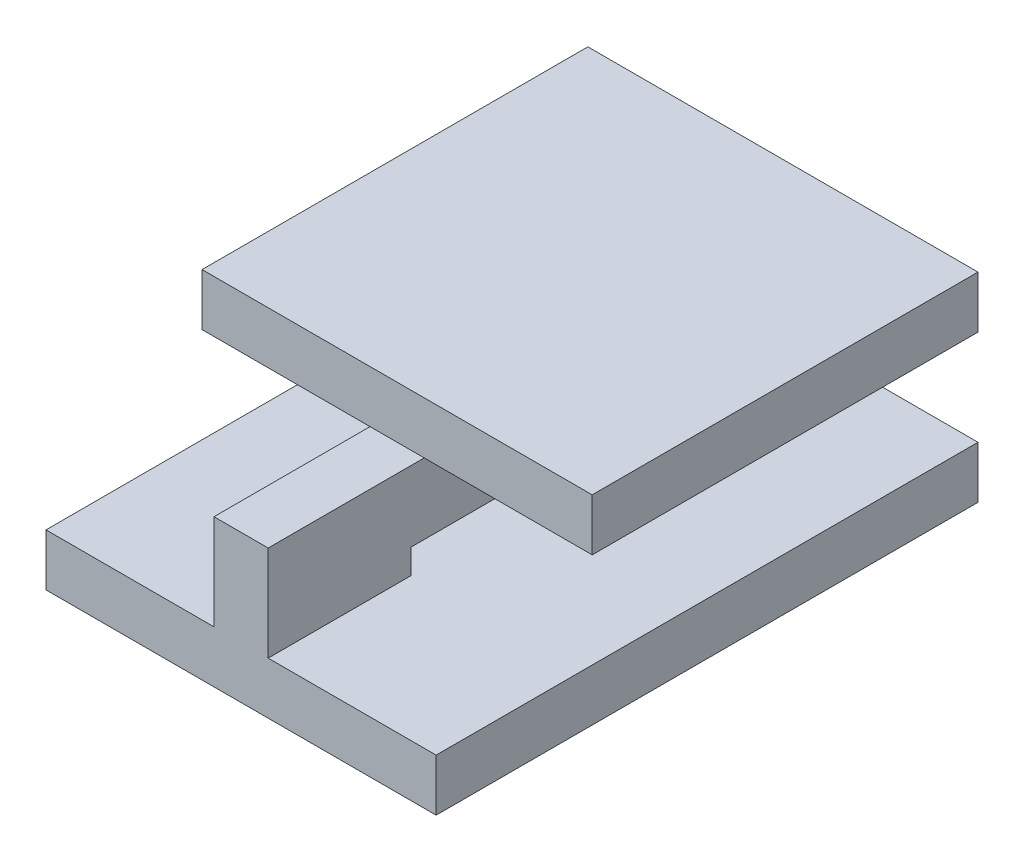
SolidWorks part; units mm, degrees
ref_plane "Front Plane" through (0, 0, 0) normal (0, 0, 1) x (1, 0, 0)
ref_plane "Top Plane" through (0, 0, 0) normal (0, 1, 0) x (1, 0, 0)
ref_plane "Right Plane" through (0, 0, 0) normal (1, 0, 0) x (0, 0, -1)
sketch "Sketch1" plane through (0, 0, 0) normal (0, 1, 0) x (1, 0, 0)
  line L1 (0, 0) -> (90, 0)
  line L2 (0, 0) -> (0, 125)
  line L3 (0, 125) -> (90, 125)
  line L4 (90, 0) -> (90, 125)
  dimension "D1" = 90
  dimension "D2" = 125
extrude "Boss-Extrude1" add sketch "Sketch1" along normal blind 12
sketch "Sketch2" plane through (0, 12, 0) normal (0, 1, 0) x (1, 0, 0)
  line L0 (0, 0) -> (90, 0) construction
  line L1 (38.75, 0) -> (51.25, 0)
  line L2 (38.75, 0) -> (38.75, 125)
  line L3 (38.75, 125) -> (51.25, 125)
  line L4 (51.25, 0) -> (51.25, 125)
  line L5 (90, 125) -> (0, 125) construction
  point P8 (45, 0)
  point P9 (45, 0)
  dimension "D1" = 12.5
extrude "Boss-Extrude2" add sketch "Sketch2" along normal blind 22
sketch "Sketch3" plane through (0, 34, 0) normal (0, 1, 0) x (1, 0, 0)
  line L1 (0, 125) -> (90, 125)
  line L2 (0, 125) -> (0, 36)
  line L3 (0, 36) -> (90, 36)
  line L4 (90, 125) -> (90, 36)
  line L5 (38.75, 125) -> (0, 125) construction
  line L6 (45, 125) -> (45, 0)
  line L8 (51.25, 125) -> (38.75, 125) construction
  line L9 (38.75, 0) -> (51.25, 0) construction
  point P15 (45, 125)
  line M7 (38.75, 125) -> (38.75, 0)
  line M9 (51.25, 0) -> (51.25, 125)
  line M10 (51.25, 125) -> (38.75, 125)
  dimension "D1" = 89
  dimension "D2" = 90
extrude "Boss-Extrude3" add sketch "Sketch3" along normal blind 12 contours L4 L1 L3 M9 | L2 L3 L1 M7 | L6 L1 L3 M7 | L6 L3 M10 M9 region at (19.375, 34, -80.5) region at (41.875, 34, -80.5) region at (48.125, 34, -80.5) region at (70.625, 34, -80.5)
sketch "Sketch4" plane through (51.25, 0, 0) normal (1, 0, 0) x (0, 0, -1)
  line L1 (125, 12) -> (32.9566, 12)
  line L2 (125, 12) -> (125, 17.6974)
  line L3 (125, 17.6974) -> (32.9566, 17.6974)
  line L4 (32.9566, 12) -> (32.9566, 17.6974)
extrude "Cut-Extrude1" cut sketch "Sketch4" against normal through all
sketch "Sketch5" plane through (0, 0, -125) normal (0, 0, -1) x (-1, 0, 0)
  line L0 (-38.75, 34) -> (-38.75, 17.6974) construction
  line L1 (-51.25, 34) -> (-38.75, 34)
  line L2 (-51.25, 34) -> (-51.25, 30.9466)
  line L3 (-51.25, 30.9466) -> (-38.75, 30.9466)
  line L4 (-38.75, 34) -> (-38.75, 30.9466)
extrude "Cut-Extrude2" cut sketch "Sketch5" against normal blind 60
